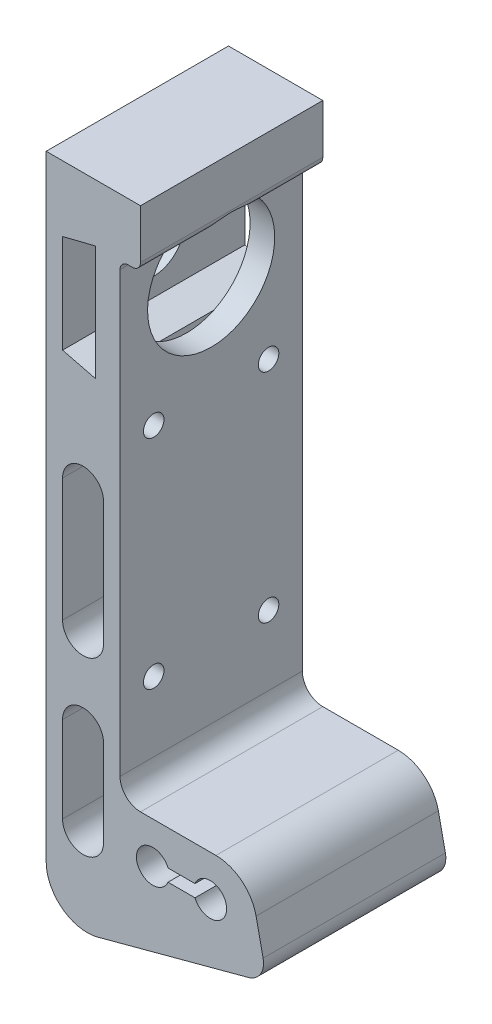
SolidWorks part; units mm, degrees
ref_plane "Front Plane" through (0, 0, 0) normal (0, 0, 1) x (1, 0, 0)
ref_plane "Top Plane" through (0, 0, 0) normal (0, 1, 0) x (1, 0, 0)
ref_plane "Right Plane" through (0, 0, 0) normal (1, 0, 0) x (0, 0, -1)
sketch "Sketch1" plane through (0, 0, 0) normal (0, 0, 1) x (1, 0, 0)
  line L0 (0, 28) -> (0, -122)
  line L1 (12.5882, -131.6593) -> (49.2941, -121.8239)
  line L2 (52.8907, -115.9548) -> (51.1831, -107.9209)
  line L3 (41.4016, -100) -> (23, -100)
  line L4 (18, -95) -> (18, 12)
  line L5 (9, 28) -> (9, -131.9499) construction
  line L6 (0, 28) -> (18, 28)
  line L7 (10, -132) -> (-10.3131, -132) construction
  line L8 (53, -128.0669) -> (53, -89.8097) construction
  line L9 (4, -111) -> (4, -90)
  line L10 (14, -90) -> (14, -111)
  line L11 (9, -69) -> (9, -39) construction
  line L12 (4, -69) -> (4, -39)
  line L13 (14, -69) -> (14, -39)
  line L14 (26, -110) -> (40, -110) construction
  line L15 (29.7081, -108.5) -> (36.2919, -108.5)
  line L16 (29.7081, -111.5) -> (36.2919, -111.5)
  line L17 (4, 12) -> (4, -12)
  line L18 (4, -12) -> (12, -14)
  line L19 (12, -14) -> (12, 14)
  line L20 (12, 14) -> (4, 12)
  line L21 (4, 0) -> (12, 0) construction
  line L22 (18, 28) -> (23, 28)
  line L23 (23, 28) -> (23, 16)
  line L24 (21, 14) -> (20, 14)
  arc A0 (0, -122) -> (12.5882, -131.6593) centre (10, -122) ccw
  arc A1 (49.2941, -121.8239) -> (52.8907, -115.9548) centre (48, -116.9943) ccw
  arc A2 (51.1831, -107.9209) -> (41.4016, -100) centre (41.4016, -110) ccw
  arc A3 (23, -100) -> (18, -95) centre (23, -95) cw
  arc A4 (4, -111) -> (14, -111) centre (9, -111) ccw
  arc A5 (14, -90) -> (4, -90) centre (9, -90) ccw
  arc A6 (4, -69) -> (14, -69) centre (9, -69) ccw
  arc A7 (14, -39) -> (4, -39) centre (9, -39) ccw
  arc A8 (29.7081, -108.5) -> (29.7081, -111.5) centre (26, -110) ccw
  arc A9 (36.2919, -111.5) -> (36.2919, -108.5) centre (40, -110) ccw
  arc A10 (20, 14) -> (18, 12) centre (20, 12) ccw
  arc A11 (23, 16) -> (21, 14) centre (21, 16) cw
  point P23 (9, -116)
  point P24 (9, -85)
  point P31 (9, -54)
  point P36 (9, -74)
  point P41 (9, -34)
  point P48 (12, 0)
  point P49 (4, 0)
  point P59 (23, 14)
  dimension "D1" = 10
  dimension "D2" = 160
  dimension "D5" = 5
  dimension "D8" = 5
  dimension "D9" = 10
  dimension "D12" = 10
  dimension "D13" = 10
  dimension "D17" = 5
  dimension "D19" = 8
  dimension "D22" = 8
  dimension "D31" = 2
  dimension "D3" = 53
  dimension "D4" = 18
  dimension "D6" = 32
  dimension "D7" = 15
  dimension "D10" = 12
  dimension "D11" = 28
  dimension "D14" = 31
  dimension "D15" = 16
  dimension "D16" = 11
  dimension "D18" = 40
  dimension "D20" = 26
  dimension "D21" = 10
  dimension "D23" = 40
  dimension "D24" = 3
  dimension "D25" = 24
  dimension "D26" = 28
  dimension "D27" = 8
  dimension "D28" = 4
  dimension "D29" = 5
  dimension "D30" = 14
extrude "Boss-Extrude1" add sketch "Sketch1" along normal mid plane 44.45
sketch "Sketch2" plane through (0, 0, 0) normal (1, 0, 0) x (0, 0, -1)
  line L1 (-14, -25) -> (14, -25) construction
  line L2 (-14, -25) -> (-14, -78) construction
  line L3 (-14, -78) -> (14, -78) construction
  line L4 (14, -25) -> (14, -78) construction
  line L5 (-14, -25) -> (14, -78) construction
  line L6 (-14, -78) -> (14, -25) construction
  circle A0 centre (14, -78) radius 2.5
  circle A1 centre (-14, -78) radius 2.5
  circle A2 centre (-14, -25) radius 2.5
  circle A3 centre (14, -25) radius 2.5
  circle A4 centre (0, 0) radius 15.5
  circle A5 centre (0, 0) radius 7.5
  point P4 (0, -51.5)
  point P13 (0, 0)
  dimension "D4" = 5
  dimension "D5" = 5
  dimension "D6" = 5
  dimension "D7" = 5
  dimension "D8" = 31
  dimension "D9" = 15
  dimension "D1" = 28
  dimension "D2" = 53
  dimension "D3" = 25
extrude "Cut-Extrude5" cut sketch "Sketch2" against normal up to surface (-18 mm away) contours A5 | A3 | A2 | A1 | A0 up to face at (18, -41.5, 0)
extrude "Cut-Extrude7" cut sketch "Sketch2<8>" along normal through all from surface contours A4 starting at face at (12, 0, 7.5)
sketch "Sketch2<8>" plane through (0, 0, 0) normal (1, 0, 0) x (0, 0, -1) same geometry as "Sketch2"
